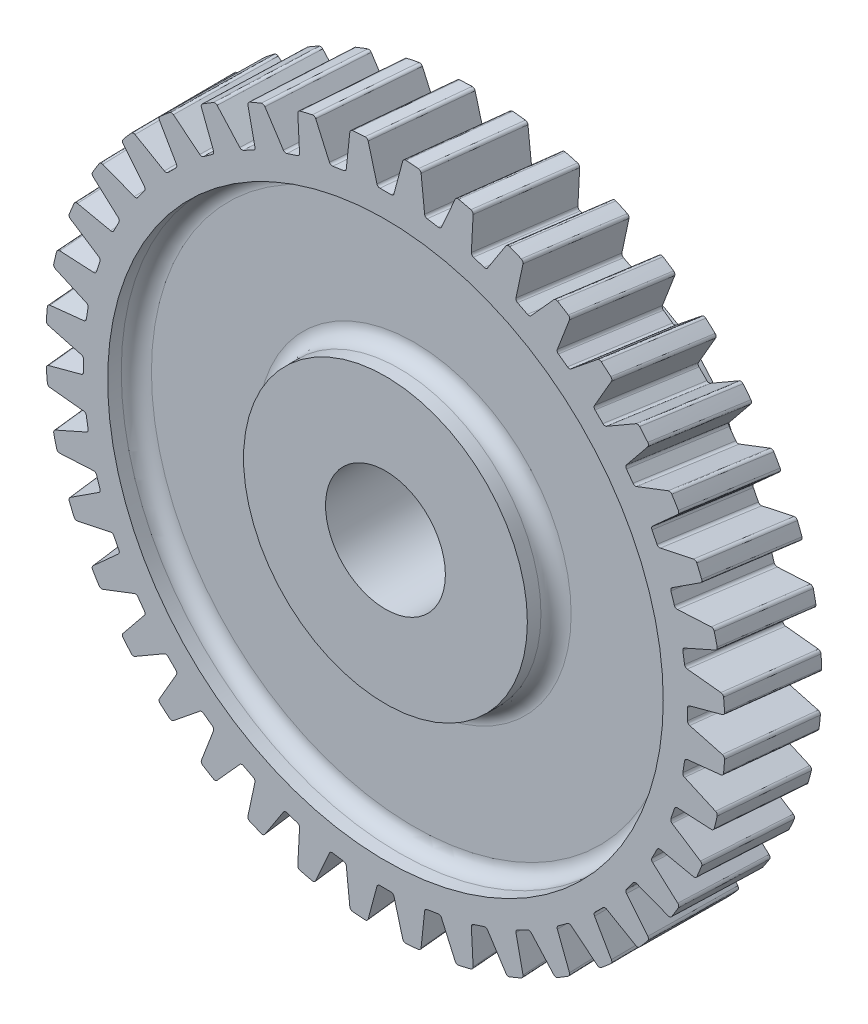
SolidWorks part; units mm, degrees
note: '?' marks a value the reader was unsure of.
ref_plane "Front Plane" through (0, 0, 0) normal (0, 0, 1) x (1, 0, 0)
ref_plane "Top Plane" through (0, 0, 0) normal (0, 1, 0) x (1, 0, 0)
ref_plane "Right Plane" through (0, 0, 0) normal (1, 0, 0) x (0, 0, -1)
sketch "Sketch2" plane through (0, 0, 0) normal (1, 0, 0) x (0, 0, -1)
  line L0 (0, 0) -> (0, 22.5) construction
  line L1 (11, 3.9688) -> (-3.2, 3.9687)
  line L2 (-3.2, 3.9687) -> (-3.2, 9.4)
  line L3 (-3.2, 9.4) -> (-1.3, 9.4)
  line L4 (-1.3, 9.4) -> (-1.3, 18.4)
  line L5 (-1.3, 18.4) -> (-3.2, 18.4)
  line L6 (-3.2, 18.4) -> (-3.2, 22.5)
  line L7 (-3.2, 22.5) -> (3.2, 22.5)
  line L8 (3.2, 18.4) -> (3.2, 22.5)
  line L9 (1.3, 18.4) -> (3.2, 18.4)
  line L10 (1.3, 9.4) -> (1.3, 18.4)
  line L11 (3.2, 9.4) -> (1.3, 9.4)
  line L12 (3.2, 9.4) -> (11, 9.4)
  line L13 (11, 9.4) -> (11, 3.9688)
  line L14 (0, 0) -> (14.174, 0) construction
  dimension "D1" = 14.2
  dimension "D2" = 3.2
  dimension "D3" = 4.5
  dimension "D4" = 7.9375
  dimension "D5" = 9.4
  dimension "D6" = 9
  dimension "D7" = 22.5
  dimension "D8" = 6.4
revolve "Revolve1" add sketch "Sketch2" angle 360 about L14
fillet "Fillet1" radius 1 4 edges at (18.4, 0, 1.3) (9.4, 0, 1.3) (9.4, 0, -1.3) (18.4, 0, -1.3)
sketch "Sketch3" plane through (0, 0, 3.2) normal (0, 0, 1) x (1, 0, 0)
  line L0 (0, 22.6922) -> (0, 20) construction
  line L1 (-0.525, 20) -> (0.525, 20)
  line L2 (0.525, 20) -> (1.2464, 22.6922)
  line L3 (1.2464, 22.6922) -> (-1.2464, 22.6922)
  line L4 (-0.525, 20) -> (-1.2464, 22.6922)
  dimension "D1" = 20
  dimension "D2" = 1.05
  dimension "D3" = 15
sketch "Sketch4" plane through (0, 0, 0) normal (0, 1, 0) x (1, 0, 0)
  line L0 (0, -3.2) -> (0.691, 3.2)
  line L1 (1.2464, -3.2) -> (-1.2464, -3.2) construction
  line L2 (22.5, 3.2) -> (-22.5, 3.2) construction
sweep "Cut-Sweep1" cut profiles "Sketch3" path "Sketch4"
pattern_circular "CirPattern1" count 40 over 360 about axis through (0, 0, 0) along (0, 0, 1) of "Cut-Sweep1"
fillet "Fillet2" radius 0.2 120 edges at (1.526, 22.4482, 0.0047) (0.8705, 20, 0) (-0.8445, 22.4841, -0.0056) (-2.2689, 19.8899, 0) (-3.306, 19.7257, 0) (-4.3514, 22.0752, -0.0056) (-5.4856, 21.8211, 0.0047) (-5.3525, 19.2901, 0) (-6.3511, 18.9657, 0) (-9.2398, 17.7386, 0) (-11.9602, 19.0579, 0.0047) (-11.0515, 16.692, 0) (-13.8991, 17.6936, -0.0056) (-14.2691, 14.0152, 0) (-16.4959, 15.3015, -0.0056) (-17.264, 14.4292, 0.0047) (-15.6687, 12.4599, 0) (-16.2859, 11.6105, 0) (-18.6865, 12.5326, -0.0056) (-17.9016, 8.9199, 0) (-20.4169, 9.4551, -0.0056) (-20.878, 8.3882, 0.0047) (-18.7521, 7.0082, 0) (-19.0766, 6.0096, 0) (-21.6447, 6.1448, -0.0056) (-21.9331, 5.0188, 0.0047) (-19.6176, 3.9885, 0) (-19.7818, 2.9514, 0) (-22.4482, 1.526, 0.0047) (-20, 0.8705, 0) (-20, -0.1795, 0) (-22.4841, -0.8445, -0.0056) (-22.4105, -2.0045, 0.0047) (-19.8899, -2.2689, 0) (-19.7257, -3.306, 0) (-22.0752, -4.3514, -0.0056) (-21.8211, -5.4856, 0.0047) (-18.9657, -6.3511, 0) (-20.6943, -8.8316, 0.0047) (-18.2153, -8.3042, 0) (-17.7386, -9.2398, 0) (-19.6501, -10.9601, -0.0056) (-19.0579, -11.9602, 0.0047) (-16.692, -11.0515, 0) (-16.0748, -11.9009, 0) (-17.6936, -13.8991, -0.0056) (-16.9523, -14.7943, 0.0047) (-14.7577, -13.5266, 0) (-14.0152, -14.2691, 0) (-12.4599, -15.6687, 0) (-11.5509, -19.3087, 0.0047) (-8.9199, -17.9016, 0) (-7.0082, -18.7521, 0) (-6.0096, -19.0766, 0) (-6.1448, -21.6447, -0.0056) (-3.9885, -19.6176, 0) (-2.6832, -22.3394, -0.0056) (-1.526, -22.4482, 0.0047) (-0.8705, -20, 0) (0.1795, -20, 0) (0.8445, -22.4841, -0.0056) (2.0045, -22.4105, 0.0047) (2.2689, -19.8899, 0) (3.306, -19.7257, 0) (4.3514, -22.0752, -0.0056) (5.4856, -21.8211, 0.0047) (5.3525, -19.2901, 0) (6.3511, -18.9657, 0) (7.7512, -21.1227, -0.0056) (8.8316, -20.6943, 0.0047) (8.3042, -18.2153, 0) (9.2398, -17.7386, 0) (11.9602, -19.0579, 0.0047) (13.8991, -17.6936, -0.0056) (14.7943, -16.9523, 0.0047) (14.2691, -14.0152, 0) (16.4959, -15.3015, -0.0056) (16.2859, -11.6105, 0) (18.6865, -12.5326, -0.0056) (17.4249, -9.8554, 0) (17.9016, -8.9199, 0) (20.4169, -9.4551, -0.0056) (20.878, -8.3882, 0.0047) (21.6447, -6.1448, -0.0056) (21.9331, -5.0188, 0.0047) (22.3394, -2.6832, -0.0056) (22.4482, -1.526, 0.0047) (20, -0.8705, 0) (20, 0.1795, 0) (22.4841, 0.8445, -0.0056) (22.4105, 2.0045, 0.0047) (19.8899, 2.2689, 0) (19.7257, 3.306, 0) (22.0752, 4.3514, -0.0056) (21.8211, 5.4856, 0.0047) (19.2901, 5.3525, 0) (18.9657, 6.3511, 0) (20.6943, 8.8316, 0.0047) (18.2153, 8.3042, 0) (17.7386, 9.2398, 0) (19.6501, 10.9601, -0.0056) (19.0579, 11.9602, 0.0047) (16.692, 11.0515, 0) (16.0748, 11.9009, 0) (17.6936, 13.8991, -0.0056) (16.9523, 14.7943, 0.0047) (14.7577, 13.5266, 0) (14.0152, 14.2691, 0) (15.3015, 16.4959, -0.0056) (14.4292, 17.264, 0.0047) (12.4599, 15.6687, 0) (12.5326, 18.6865, -0.0056) (11.5509, 19.3087, 0.0047) (9.8554, 17.4249, 0) (9.4551, 20.4169, -0.0056) (7.0082, 18.7521, 0) (6.1448, 21.6447, -0.0056) (5.0188, 21.9331, 0.0047) (2.9514, 19.7818, 0) (2.6832, 22.3394, -0.0056)
ref_axis "gear axis" through (0, 0, -11) along (0, 0, 1)?
